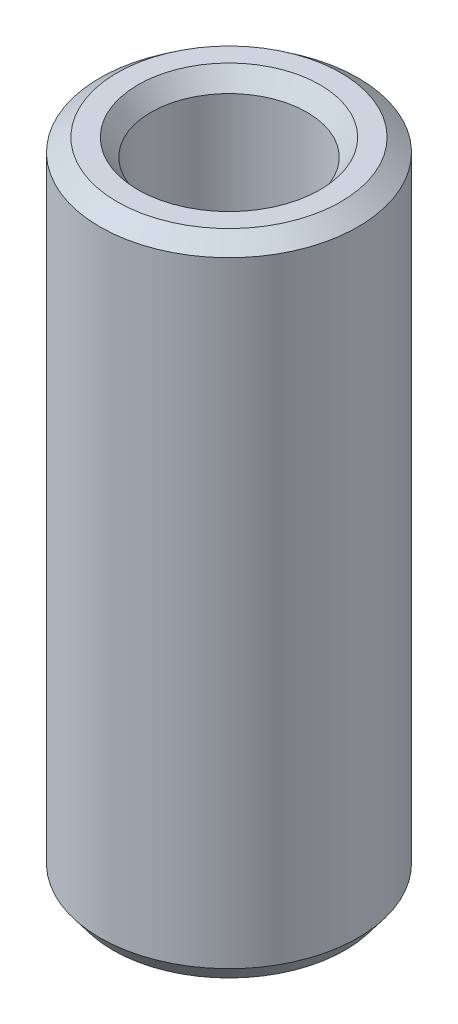
SolidWorks part; units mm, degrees
ref_plane "Front Plane" through (0, 0, 0) normal (0, 0, 1) x (1, 0, 0)
ref_plane "Top Plane" through (0, 0, 0) normal (0, 1, 0) x (1, 0, 0)
ref_plane "Right Plane" through (0, 0, 0) normal (1, 0, 0) x (0, 0, -1)
sketch "Sketch1" plane through (0, 0, 0) normal (0, 1, 0) x (1, 0, 0)
  circle A0 centre (0, 0) radius 30
  dimension "SLEEVE_OD" = 60
extrude "Boss-Extrude1" add sketch "Sketch1" along normal blind 150.1566
sketch "Sketch2" plane through (0, 0, 0) normal (0, 1, 0) x (1, 0, 0)
  circle A0 centre (0, 0) radius 18.124
  dimension "BORE_D" = 36.2481
extrude "Cut-Extrude1" cut sketch "Sketch2" along normal through all
chamfer "Chamfer1" distance 3.0321 angle 52.92 4 edges at (0, 150.1566, 18.124) (0, 0, 18.124) (0, 0, 30) (0, 150.1566, 30) first distance on face at (0, 150.1566, 18.124) first distance on face at (0, 0, 18.124) first distance on face at (0, 150.1566, 30)
